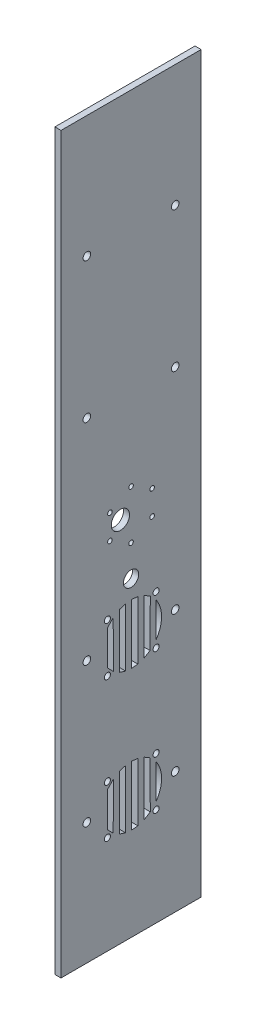
SolidWorks part; units mm, degrees
ref_plane "Alzado" through (0, 0, 0) normal (0, 0, 1) x (1, 0, 0)
ref_plane "Planta" through (0, 0, 0) normal (0, 1, 0) x (1, 0, 0)
ref_plane "Vista lateral" through (0, 0, 0) normal (1, 0, 0) x (0, 0, -1)
sketch "Croquis3" plane through (-90.5016, 0, 0) normal (-1, 0, 0) x (0, 0, 1)
  line L0 (-58.4589, 795.4218) -> (-58.4589, 772.8149)
  line L1 (-88, 703.6284) -> (4, 703.6284)
  line L2 (-88, 703.6284) -> (-88, 1185.6284)
  line L3 (-88, 1185.6284) -> (4, 1185.6284)
  line L4 (4, 703.6284) -> (4, 1185.6284)
  line L5 (-50.4589, 802.0004) -> (-50.4589, 766.2363)
  line L6 (-50.4589, 766.2363) -> (-54.6424, 768.7778)
  line L7 (-54.6424, 768.7778) -> (-54.4589, 799.6028)
  line L8 (-54.4589, 799.6028) -> (-50.4589, 802.0004)
  line L9 (-46.4589, 803.2956) -> (-46.4589, 764.941)
  line L10 (-46.4589, 764.941) -> (-42.4589, 764.5283)
  line L11 (-42.4589, 764.5283) -> (-42.4589, 803.7083)
  line L12 (-42.4589, 803.7083) -> (-46.4589, 803.2956)
  line L13 (-38.4589, 803.2956) -> (-38.4589, 764.941)
  line L14 (-38.4589, 764.941) -> (-34.4589, 766.2363)
  line L15 (-34.4589, 766.2363) -> (-34.4589, 802.0004)
  line L16 (-34.4589, 802.0004) -> (-38.4589, 803.2956)
  line L17 (-30.4589, 799.6028) -> (-30.2754, 768.7778)
  line L18 (-30.2754, 768.7778) -> (-26.4589, 772.8149)
  line L19 (-26.4589, 772.8149) -> (-26.4589, 795.4218)
  line L20 (-26.4589, 795.4218) -> (-30.4589, 799.6028)
  line L21 (-26.4589, 887.4218) -> (-30.2754, 891.4588)
  line L22 (-30.2754, 891.4588) -> (-30.4589, 860.6339)
  line L24 (-30.4589, 860.6339) -> (-26.4589, 864.8149)
  line L25 (-26.4589, 864.8149) -> (-26.4589, 887.4218)
  line L26 (-34.4589, 894.0004) -> (-38.4589, 895.2956)
  line L27 (-38.4589, 895.2956) -> (-38.4589, 856.941)
  line L28 (-38.4589, 856.941) -> (-34.4589, 858.2363)
  line L29 (-34.4589, 858.2363) -> (-34.4589, 894.0004)
  line L30 (-42.4589, 895.7083) -> (-46.4589, 895.2956)
  line L31 (-46.4589, 895.2956) -> (-46.4589, 856.941)
  line L32 (-46.4589, 856.941) -> (-42.4589, 856.5283)
  line L33 (-42.4589, 856.5283) -> (-42.4589, 895.7083)
  line L34 (-50.4589, 894.0004) -> (-54.6424, 891.4588)
  line L35 (-54.6424, 891.4588) -> (-54.4589, 860.6339)
  line L36 (-54.4589, 860.6339) -> (-50.4589, 858.2363)
  line L37 (-50.4589, 858.2363) -> (-50.4589, 894.0004)
  circle A0 centre (-71.0005, 783.6284) radius 2.5
  circle A1 centre (-58.4589, 768.1183) radius 2
  circle A2 centre (-58.4589, 800.1183) radius 2
  circle A3 centre (-26.4589, 800.1183) radius 2
  circle A4 centre (-26.4589, 768.1183) radius 2
  circle A5 centre (-13.0005, 783.6284) radius 2.5
  circle A6 centre (-58.4589, 860.1183) radius 2
  circle A7 centre (-58.4589, 892.1183) radius 2
  circle A8 centre (-26.4589, 892.1183) radius 2
  circle A9 centre (-26.4589, 860.1183) radius 2
  circle A10 centre (-13.0005, 875.6284) radius 2.5
  circle A11 centre (-42.0005, 907.7284) radius 5
  circle A12 centre (-42.0005, 928.1128) radius 1.5
  circle A13 centre (-35.0005, 944.6284) radius 6
  circle A14 centre (-28.1373, 936.1167) radius 1.5
  circle A15 centre (-28.1373, 952.1245) radius 1.5
  circle A16 centre (-42.0005, 960.1284) radius 1.5
  circle A17 centre (-55.8636, 952.1245) radius 1.5
  circle A18 centre (-55.8636, 936.1167) radius 1.5
  circle A19 centre (-71.0005, 1013.6284) radius 2.5
  circle A20 centre (-13.0005, 1013.6284) radius 2.5
  circle A21 centre (-13.0005, 1105.6284) radius 2.5
  circle A22 centre (-71.0005, 1105.6284) radius 2.5
  circle A23 centre (-71.0005, 875.6284) radius 2.5
  arc A24 (-58.4589, 772.8149) -> (-58.4589, 795.4218) centre (-42.4589, 784.1183) cw
extrude "Saliente-Extruir1" add sketch "Croquis3" along normal blind 4
sketch "Croquis4" plane through (-90.5016, 0, 0) normal (1, 0, 0) x (0, 0, -1)
  line L0 (58.4589, 887.4218) -> (58.4589, 864.8149)
  arc A0 (58.4589, 864.8149) -> (58.4589, 887.4218) centre (42.4589, 876.1183) ccw
extrude "Cortar-Extruir1" cut sketch "Croquis4" against normal blind 10
